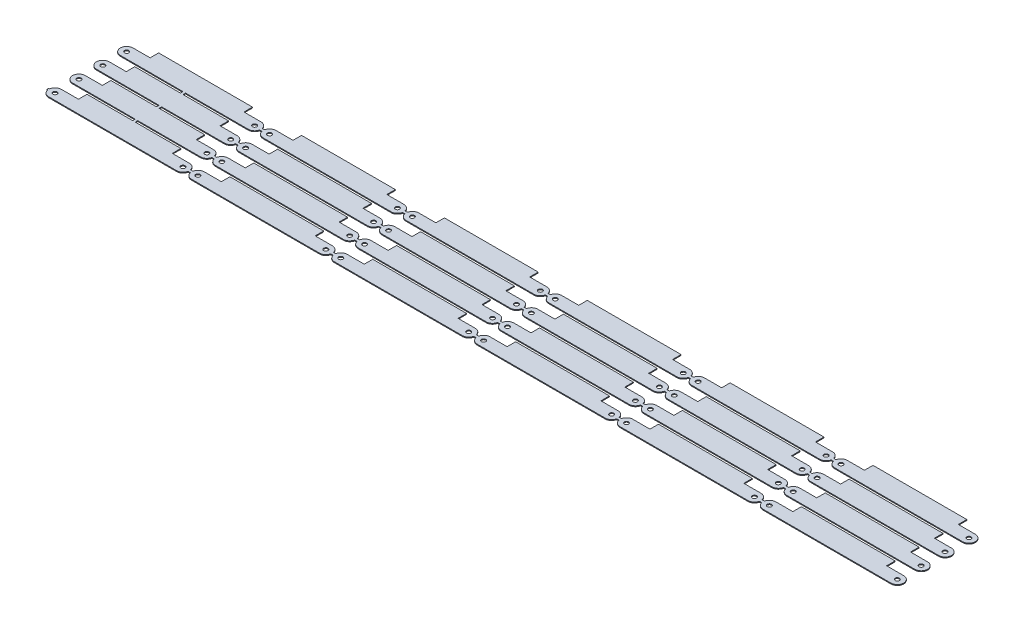
SolidWorks part; units mm, degrees
ref_plane "Front Plane" through (0, 0, 0) normal (0, 0, 1) x (1, 0, 0)
ref_plane "Top Plane" through (0, 0, 0) normal (0, 1, 0) x (1, 0, 0)
ref_plane "Right Plane" through (0, 0, 0) normal (1, 0, 0) x (0, 0, -1)
sketch "Sketch1" plane through (0, 0, 0) normal (0, 1, 0) x (1, 0, 0)
  line L0 (0, 0) -> (150, 0) construction
  line L1 (0, 7.5) -> (20, 7.5)
  line L2 (0, 7.5) -> (150, 7.5) construction
  line L3 (0, 7.5) -> (0, -7.5) construction
  line L4 (0, -7.5) -> (150, -7.5)
  line L5 (150, 7.5) -> (150, -7.5) construction
  line L6 (0, 7.5) -> (150, -7.5) construction
  line L7 (0, -7.5) -> (150, 7.5) construction
  line L8 (20, 7.5) -> (20, 17.5)
  line L9 (20, 17.5) -> (130, 17.5)
  line L10 (130, 17.5) -> (130, 7.5)
  line L11 (130, 7.5) -> (150, 7.5)
  line L12 (75, 0) -> (75, 17.5) construction
  line L13 (75, 17.5) -> (75, 20.5) construction
  line L14 (73.5, 17.5) -> (73.5, 20.5)
  line L15 (73.5, 20.5) -> (76.5, 20.5)
  line L16 (76.5, 20.5) -> (76.5, 17.5)
  line L17 (150, 0) -> (157.5, 0) construction
  line L18 (157.5, 0) -> (160.5, 0) construction
  line L19 (160.5, 1.5) -> (160.5, -1.5)
  line L20 (160.5, 1.5) -> (157.3485, 1.5)
  line L21 (160.5, -1.5) -> (157.3485, -1.5)
  line L22 (167.5, -7.5) -> (317.5, -7.5)
  line L23 (187.5, 17.5) -> (297.5, 17.5)
  line L24 (187.5, 7.5) -> (187.5, 17.5)
  line L25 (167.5, 7.5) -> (187.5, 7.5)
  line L26 (297.5, 7.5) -> (317.5, 7.5)
  line L27 (328, -1.5) -> (324.8485, -1.5)
  line L28 (328, 1.5) -> (324.8485, 1.5)
  line L29 (328, 1.5) -> (328, -1.5)
  line L30 (297.5, 17.5) -> (297.5, 7.5)
  line L31 (-7.5, 0) -> (-8.433, 0) construction
  line L32 (-8.433, 1) -> (-8.433, -1)
  line L33 (-8.433, -1) -> (-7.433, -1)
  line L34 (335, -7.5) -> (485, -7.5)
  line L35 (355, 17.5) -> (465, 17.5)
  line L36 (355, 7.5) -> (355, 17.5)
  line L37 (335, 7.5) -> (355, 7.5)
  line L38 (465, 7.5) -> (485, 7.5)
  line L39 (495.5, -1.5) -> (492.3485, -1.5)
  line L40 (495.5, 1.5) -> (492.3485, 1.5)
  line L41 (495.5, 1.5) -> (495.5, -1.5)
  line L42 (465, 17.5) -> (465, 7.5)
  line L44 (-8.433, 1) -> (-7.433, 1)
  line L46 (502.5, -7.5) -> (652.5, -7.5)
  line L47 (522.5, 17.5) -> (632.5, 17.5)
  line L48 (522.5, 7.5) -> (522.5, 17.5)
  line L49 (502.5, 7.5) -> (522.5, 7.5)
  line L50 (632.5, 7.5) -> (652.5, 7.5)
  line L51 (663, -1.5) -> (659.8485, -1.5)
  line L52 (663, 1.5) -> (659.8485, 1.5)
  line L53 (663, 1.5) -> (663, -1.5)
  line L54 (632.5, 17.5) -> (632.5, 7.5)
  line L58 (670, -7.5) -> (820, -7.5)
  line L59 (690, 17.5) -> (800, 17.5)
  line L60 (690, 7.5) -> (690, 17.5)
  line L61 (670, 7.5) -> (690, 7.5)
  line L62 (800, 7.5) -> (820, 7.5)
  line L63 (830.5, -1.5) -> (827.3485, -1.5)
  line L64 (830.5, 1.5) -> (827.3485, 1.5)
  line L65 (830.5, 1.5) -> (830.5, -1.5)
  line L66 (800, 17.5) -> (800, 7.5)
  line L70 (837.5, -7.5) -> (987.5, -7.5)
  line L71 (857.5, 17.5) -> (967.5, 17.5)
  line L72 (857.5, 7.5) -> (857.5, 17.5)
  line L73 (837.5, 7.5) -> (857.5, 7.5)
  line L74 (967.5, 7.5) -> (987.5, 7.5)
  line L78 (967.5, 17.5) -> (967.5, 7.5)
  line L82 (167.5, 20.5) -> (317.5, 20.5)
  line L83 (187.5, 45.5) -> (297.5, 45.5)
  line L84 (187.5, 35.5) -> (187.5, 45.5)
  line L85 (167.5, 35.5) -> (187.5, 35.5)
  line L86 (297.5, 35.5) -> (317.5, 35.5)
  line L87 (328, 26.5) -> (324.8485, 26.5)
  line L88 (328, 29.5) -> (324.8485, 29.5)
  line L89 (328, 29.5) -> (328, 26.5)
  line L90 (297.5, 45.5) -> (297.5, 35.5)
  line L94 (335, 20.5) -> (485, 20.5)
  line L95 (355, 45.5) -> (465, 45.5)
  line L96 (355, 35.5) -> (355, 45.5)
  line L97 (335, 35.5) -> (355, 35.5)
  line L98 (465, 35.5) -> (485, 35.5)
  line L99 (495.5, 26.5) -> (492.3485, 26.5)
  line L100 (495.5, 29.5) -> (492.3485, 29.5)
  line L101 (495.5, 29.5) -> (495.5, 26.5)
  line L102 (465, 45.5) -> (465, 35.5)
  line L106 (502.5, 20.5) -> (652.5, 20.5)
  line L107 (522.5, 45.5) -> (632.5, 45.5)
  line L108 (522.5, 35.5) -> (522.5, 45.5)
  line L109 (502.5, 35.5) -> (522.5, 35.5)
  line L110 (632.5, 35.5) -> (652.5, 35.5)
  line L111 (663, 26.5) -> (659.8485, 26.5)
  line L112 (663, 29.5) -> (659.8485, 29.5)
  line L113 (663, 29.5) -> (663, 26.5)
  line L114 (632.5, 45.5) -> (632.5, 35.5)
  line L118 (670, 20.5) -> (820, 20.5)
  line L119 (690, 45.5) -> (800, 45.5)
  line L120 (690, 35.5) -> (690, 45.5)
  line L121 (670, 35.5) -> (690, 35.5)
  line L122 (800, 35.5) -> (820, 35.5)
  line L123 (830.5, 26.5) -> (827.3485, 26.5)
  line L124 (830.5, 29.5) -> (827.3485, 29.5)
  line L125 (830.5, 29.5) -> (830.5, 26.5)
  line L126 (800, 45.5) -> (800, 35.5)
  line L130 (837.5, 20.5) -> (987.5, 20.5)
  line L131 (857.5, 45.5) -> (967.5, 45.5)
  line L132 (857.5, 35.5) -> (857.5, 45.5)
  line L133 (837.5, 35.5) -> (857.5, 35.5)
  line L134 (967.5, 35.5) -> (987.5, 35.5)
  line L138 (967.5, 45.5) -> (967.5, 35.5)
  line L142 (167.5, 48.5) -> (317.5, 48.5)
  line L143 (187.5, 73.5) -> (297.5, 73.5)
  line L144 (187.5, 63.5) -> (187.5, 73.5)
  line L145 (167.5, 63.5) -> (187.5, 63.5)
  line L146 (297.5, 63.5) -> (317.5, 63.5)
  line L147 (328, 54.5) -> (324.8485, 54.5)
  line L148 (328, 57.5) -> (324.8485, 57.5)
  line L149 (328, 57.5) -> (328, 54.5)
  line L150 (297.5, 73.5) -> (297.5, 63.5)
  line L154 (335, 48.5) -> (485, 48.5)
  line L155 (355, 73.5) -> (465, 73.5)
  line L156 (355, 63.5) -> (355, 73.5)
  line L157 (335, 63.5) -> (355, 63.5)
  line L158 (465, 63.5) -> (485, 63.5)
  line L159 (495.5, 54.5) -> (492.3485, 54.5)
  line L160 (495.5, 57.5) -> (492.3485, 57.5)
  line L161 (495.5, 57.5) -> (495.5, 54.5)
  line L162 (465, 73.5) -> (465, 63.5)
  line L166 (502.5, 48.5) -> (652.5, 48.5)
  line L167 (522.5, 73.5) -> (632.5, 73.5)
  line L168 (522.5, 63.5) -> (522.5, 73.5)
  line L169 (502.5, 63.5) -> (522.5, 63.5)
  line L170 (632.5, 63.5) -> (652.5, 63.5)
  line L171 (663, 54.5) -> (659.8485, 54.5)
  line L172 (663, 57.5) -> (659.8485, 57.5)
  line L173 (663, 57.5) -> (663, 54.5)
  line L174 (632.5, 73.5) -> (632.5, 63.5)
  line L178 (670, 48.5) -> (820, 48.5)
  line L179 (690, 73.5) -> (800, 73.5)
  line L180 (690, 63.5) -> (690, 73.5)
  line L181 (670, 63.5) -> (690, 63.5)
  line L182 (800, 63.5) -> (820, 63.5)
  line L183 (830.5, 54.5) -> (827.3485, 54.5)
  line L184 (830.5, 57.5) -> (827.3485, 57.5)
  line L185 (830.5, 57.5) -> (830.5, 54.5)
  line L186 (800, 73.5) -> (800, 63.5)
  line L190 (837.5, 48.5) -> (987.5, 48.5)
  line L191 (857.5, 73.5) -> (967.5, 73.5)
  line L192 (857.5, 63.5) -> (857.5, 73.5)
  line L193 (837.5, 63.5) -> (857.5, 63.5)
  line L194 (967.5, 63.5) -> (987.5, 63.5)
  line L198 (967.5, 73.5) -> (967.5, 63.5)
  line L202 (167.5, 76.5) -> (317.5, 76.5)
  line L203 (187.5, 101.5) -> (297.5, 101.5)
  line L204 (187.5, 91.5) -> (187.5, 101.5)
  line L205 (167.5, 91.5) -> (187.5, 91.5)
  line L206 (297.5, 91.5) -> (317.5, 91.5)
  line L207 (328, 82.5) -> (324.8485, 82.5)
  line L208 (328, 85.5) -> (324.8485, 85.5)
  line L209 (328, 85.5) -> (328, 82.5)
  line L210 (297.5, 101.5) -> (297.5, 91.5)
  line L214 (335, 76.5) -> (485, 76.5)
  line L215 (355, 101.5) -> (465, 101.5)
  line L216 (355, 91.5) -> (355, 101.5)
  line L217 (335, 91.5) -> (355, 91.5)
  line L218 (465, 91.5) -> (485, 91.5)
  line L219 (495.5, 82.5) -> (492.3485, 82.5)
  line L220 (495.5, 85.5) -> (492.3485, 85.5)
  line L221 (495.5, 85.5) -> (495.5, 82.5)
  line L222 (465, 101.5) -> (465, 91.5)
  line L226 (502.5, 76.5) -> (652.5, 76.5)
  line L227 (522.5, 101.5) -> (632.5, 101.5)
  line L228 (522.5, 91.5) -> (522.5, 101.5)
  line L229 (502.5, 91.5) -> (522.5, 91.5)
  line L230 (632.5, 91.5) -> (652.5, 91.5)
  line L231 (663, 82.5) -> (659.8485, 82.5)
  line L232 (663, 85.5) -> (659.8485, 85.5)
  line L233 (663, 85.5) -> (663, 82.5)
  line L234 (632.5, 101.5) -> (632.5, 91.5)
  line L238 (670, 76.5) -> (820, 76.5)
  line L239 (690, 101.5) -> (800, 101.5)
  line L240 (690, 91.5) -> (690, 101.5)
  line L241 (670, 91.5) -> (690, 91.5)
  line L242 (800, 91.5) -> (820, 91.5)
  line L243 (830.5, 82.5) -> (827.3485, 82.5)
  line L244 (830.5, 85.5) -> (827.3485, 85.5)
  line L245 (830.5, 85.5) -> (830.5, 82.5)
  line L246 (800, 101.5) -> (800, 91.5)
  line L250 (837.5, 76.5) -> (987.5, 76.5)
  line L251 (857.5, 101.5) -> (967.5, 101.5)
  line L252 (857.5, 91.5) -> (857.5, 101.5)
  line L253 (837.5, 91.5) -> (857.5, 91.5)
  line L254 (967.5, 91.5) -> (987.5, 91.5)
  line L258 (967.5, 101.5) -> (967.5, 91.5)
  line L262 (0, 20.5) -> (150, 20.5)
  line L263 (20, 45.5) -> (130, 45.5)
  line L264 (20, 35.5) -> (20, 45.5)
  line L265 (0, 35.5) -> (20, 35.5)
  line L266 (130, 35.5) -> (150, 35.5)
  line L267 (160.5, 26.5) -> (157.3485, 26.5)
  line L268 (160.5, 29.5) -> (157.3485, 29.5)
  line L269 (160.5, 29.5) -> (160.5, 26.5)
  line L270 (130, 45.5) -> (130, 35.5)
  line L271 (73.5, 45.5) -> (73.5, 48.5)
  line L272 (73.5, 48.5) -> (76.5, 48.5)
  line L273 (76.5, 48.5) -> (76.5, 45.5)
  line L274 (0, 48.5) -> (150, 48.5)
  line L275 (20, 73.5) -> (130, 73.5)
  line L276 (20, 63.5) -> (20, 73.5)
  line L277 (0, 63.5) -> (20, 63.5)
  line L278 (130, 63.5) -> (150, 63.5)
  line L279 (160.5, 54.5) -> (157.3485, 54.5)
  line L280 (160.5, 57.5) -> (157.3485, 57.5)
  line L281 (160.5, 57.5) -> (160.5, 54.5)
  line L282 (130, 73.5) -> (130, 63.5)
  line L283 (73.5, 73.5) -> (73.5, 76.5)
  line L284 (73.5, 76.5) -> (76.5, 76.5)
  line L285 (76.5, 76.5) -> (76.5, 73.5)
  line L286 (0, 76.5) -> (150, 76.5)
  line L287 (20, 101.5) -> (130, 101.5)
  line L288 (20, 91.5) -> (20, 101.5)
  line L289 (0, 91.5) -> (20, 91.5)
  line L290 (130, 91.5) -> (150, 91.5)
  line L291 (160.5, 82.5) -> (157.3485, 82.5)
  line L292 (160.5, 85.5) -> (157.3485, 85.5)
  line L293 (160.5, 85.5) -> (160.5, 82.5)
  line L294 (130, 101.5) -> (130, 91.5)
  line L298 (76.5, 104.5) -> (76.5, 101.5) [skipped]
  line L299 (73.5, 101.5) -> (73.5, 104.5) [skipped]
  line L300 (73.5, 104.5) -> (76.5, 104.5) [skipped]
  line L301 (241, 104.5) -> (244, 104.5) [skipped]
  line L302 (408.5, 104.5) -> (411.5, 104.5) [skipped]
  line L303 (576, 104.5) -> (579, 104.5) [skipped]
  line L304 (241, 101.5) -> (241, 104.5) [skipped]
  line L305 (244, 104.5) -> (244, 101.5) [skipped]
  line L306 (408.5, 101.5) -> (408.5, 104.5) [skipped]
  line L307 (411.5, 104.5) -> (411.5, 101.5) [skipped]
  line L308 (579, 104.5) -> (579, 101.5) [skipped]
  line L309 (576, 101.5) -> (576, 104.5) [skipped]
  line L310 (746.5, 104.5) -> (746.5, 101.5) [skipped]
  line L311 (743.5, 101.5) -> (743.5, 104.5) [skipped]
  line L312 (743.5, 104.5) -> (746.5, 104.5) [skipped]
  line L313 (911, 101.5) -> (911, 104.5) [skipped]
  line L314 (911, 104.5) -> (914, 104.5) [skipped]
  line L315 (914, 104.5) -> (914, 101.5) [skipped]
  line L316 (998, -1.5) -> (994.8485, -1.5) [skipped]
  line L317 (998, 1.5) -> (994.8485, 1.5) [skipped]
  line L318 (998, 1.5) -> (998, -1.5) [skipped]
  line L319 (998, 26.5) -> (994.8485, 26.5) [skipped]
  line L320 (998, 29.5) -> (994.8485, 29.5) [skipped]
  line L321 (998, 29.5) -> (998, 26.5) [skipped]
  line L322 (998, 54.5) -> (994.8485, 54.5) [skipped]
  line L323 (998, 57.5) -> (994.8485, 57.5) [skipped]
  line L324 (998, 57.5) -> (998, 54.5) [skipped]
  line L325 (998, 82.5) -> (994.8485, 82.5) [skipped]
  line L326 (998, 85.5) -> (994.8485, 85.5) [skipped]
  line L327 (998, 85.5) -> (998, 82.5) [skipped]
  line L328 (241, 73.5) -> (241, 76.5) [skipped]
  line L329 (244, 76.5) -> (244, 73.5) [skipped]
  line L330 (241, 76.5) -> (244, 76.5) [skipped]
  line L331 (241, 20.5) -> (244, 20.5) [skipped]
  line L332 (241, 17.5) -> (241, 20.5) [skipped]
  line L333 (244, 20.5) -> (244, 17.5) [skipped]
  line L334 (241, 45.5) -> (241, 48.5) [skipped]
  line L335 (241, 48.5) -> (244, 48.5) [skipped]
  line L336 (244, 48.5) -> (244, 45.5) [skipped]
  line L337 (408.5, 20.5) -> (411.5, 20.5) [skipped]
  line L338 (411.5, 20.5) -> (411.5, 17.5) [skipped]
  line L339 (408.5, 17.5) -> (408.5, 20.5) [skipped]
  line L340 (411.5, 48.5) -> (411.5, 45.5) [skipped]
  line L341 (408.5, 45.5) -> (408.5, 48.5) [skipped]
  line L342 (408.5, 48.5) -> (411.5, 48.5) [skipped]
  line L343 (408.5, 73.5) -> (408.5, 76.5) [skipped]
  line L344 (411.5, 76.5) -> (411.5, 73.5) [skipped]
  line L345 (408.5, 76.5) -> (411.5, 76.5) [skipped]
  line L346 (746.5, 20.5) -> (746.5, 17.5) [skipped]
  line L347 (743.5, 17.5) -> (743.5, 20.5) [skipped]
  line L348 (743.5, 20.5) -> (746.5, 20.5) [skipped]
  line L349 (746.5, 48.5) -> (746.5, 45.5) [skipped]
  line L350 (743.5, 48.5) -> (746.5, 48.5) [skipped]
  line L351 (743.5, 45.5) -> (743.5, 48.5) [skipped]
  line L352 (746.5, 76.5) -> (746.5, 73.5) [skipped]
  line L353 (743.5, 76.5) -> (746.5, 76.5) [skipped]
  line L354 (743.5, 73.5) -> (743.5, 76.5) [skipped]
  line L355 (914, 20.5) -> (914, 17.5) [skipped]
  line L356 (911, 20.5) -> (914, 20.5) [skipped]
  line L357 (911, 17.5) -> (911, 20.5) [skipped]
  line L358 (914, 48.5) -> (914, 45.5) [skipped]
  line L359 (911, 45.5) -> (911, 48.5) [skipped]
  line L360 (911, 48.5) -> (914, 48.5) [skipped]
  line L361 (914, 76.5) -> (914, 73.5) [skipped]
  line L362 (911, 76.5) -> (914, 76.5) [skipped]
  line L363 (911, 73.5) -> (911, 76.5) [skipped]
  line L364 (579, 20.5) -> (579, 17.5) [skipped]
  line L365 (576, 17.5) -> (576, 20.5) [skipped]
  line L366 (576, 20.5) -> (579, 20.5) [skipped]
  line L367 (579, 48.5) -> (579, 45.5) [skipped]
  line L368 (576, 48.5) -> (579, 48.5) [skipped]
  line L369 (576, 45.5) -> (576, 48.5) [skipped]
  line L370 (579, 76.5) -> (579, 73.5) [skipped]
  line L371 (576, 76.5) -> (579, 76.5) [skipped]
  line L372 (576, 73.5) -> (576, 76.5) [skipped]
  circle A0 centre (0, 0) radius 2.5
  circle A1 centre (150, 0) radius 2.5
  arc A2 (0, 7.5) -> (0, -7.5) centre (0, 0) ccw
  arc A3 (150, -7.5) -> (150, 7.5) centre (150, 0) ccw
  circle A4 centre (167.5, 0) radius 2.5
  arc A5 (167.5, 7.5) -> (167.5, -7.5) centre (167.5, 0) ccw
  arc A6 (317.5, -7.5) -> (317.5, 7.5) centre (317.5, 0) ccw
  circle A7 centre (317.5, 0) radius 2.5
  circle A8 centre (335, 0) radius 2.5
  arc A9 (335, 7.5) -> (335, -7.5) centre (335, 0) ccw
  arc A10 (485, -7.5) -> (485, 7.5) centre (485, 0) ccw
  circle A11 centre (485, 0) radius 2.5
  circle A12 centre (502.5, 0) radius 2.5
  arc A13 (502.5, 7.5) -> (502.5, -7.5) centre (502.5, 0) ccw
  arc A14 (652.5, -7.5) -> (652.5, 7.5) centre (652.5, 0) ccw
  circle A15 centre (652.5, 0) radius 2.5
  circle A16 centre (670, 0) radius 2.5
  arc A17 (670, 7.5) -> (670, -7.5) centre (670, 0) ccw
  arc A18 (820, -7.5) -> (820, 7.5) centre (820, 0) ccw
  circle A19 centre (820, 0) radius 2.5
  circle A20 centre (837.5, 0) radius 2.5
  arc A21 (837.5, 7.5) -> (837.5, -7.5) centre (837.5, 0) ccw
  arc A22 (987.5, -7.5) -> (987.5, 7.5) centre (987.5, 0) ccw
  circle A23 centre (987.5, 0) radius 2.5
  circle A24 centre (167.5, 28) radius 2.5
  arc A25 (167.5, 35.5) -> (167.5, 20.5) centre (167.5, 28) ccw
  arc A26 (317.5, 20.5) -> (317.5, 35.5) centre (317.5, 28) ccw
  circle A27 centre (317.5, 28) radius 2.5
  circle A28 centre (335, 28) radius 2.5
  arc A29 (335, 35.5) -> (335, 20.5) centre (335, 28) ccw
  arc A30 (485, 20.5) -> (485, 35.5) centre (485, 28) ccw
  circle A31 centre (485, 28) radius 2.5
  circle A32 centre (502.5, 28) radius 2.5
  arc A33 (502.5, 35.5) -> (502.5, 20.5) centre (502.5, 28) ccw
  arc A34 (652.5, 20.5) -> (652.5, 35.5) centre (652.5, 28) ccw
  circle A35 centre (652.5, 28) radius 2.5
  circle A36 centre (670, 28) radius 2.5
  arc A37 (670, 35.5) -> (670, 20.5) centre (670, 28) ccw
  arc A38 (820, 20.5) -> (820, 35.5) centre (820, 28) ccw
  circle A39 centre (820, 28) radius 2.5
  circle A40 centre (837.5, 28) radius 2.5
  arc A41 (837.5, 35.5) -> (837.5, 20.5) centre (837.5, 28) ccw
  arc A42 (987.5, 20.5) -> (987.5, 35.5) centre (987.5, 28) ccw
  circle A43 centre (987.5, 28) radius 2.5
  circle A44 centre (167.5, 56) radius 2.5
  arc A45 (167.5, 63.5) -> (167.5, 48.5) centre (167.5, 56) ccw
  arc A46 (317.5, 48.5) -> (317.5, 63.5) centre (317.5, 56) ccw
  circle A47 centre (317.5, 56) radius 2.5
  circle A48 centre (335, 56) radius 2.5
  arc A49 (335, 63.5) -> (335, 48.5) centre (335, 56) ccw
  arc A50 (485, 48.5) -> (485, 63.5) centre (485, 56) ccw
  circle A51 centre (485, 56) radius 2.5
  circle A52 centre (502.5, 56) radius 2.5
  arc A53 (502.5, 63.5) -> (502.5, 48.5) centre (502.5, 56) ccw
  arc A54 (652.5, 48.5) -> (652.5, 63.5) centre (652.5, 56) ccw
  circle A55 centre (652.5, 56) radius 2.5
  circle A56 centre (670, 56) radius 2.5
  arc A57 (670, 63.5) -> (670, 48.5) centre (670, 56) ccw
  arc A58 (820, 48.5) -> (820, 63.5) centre (820, 56) ccw
  circle A59 centre (820, 56) radius 2.5
  circle A60 centre (837.5, 56) radius 2.5
  arc A61 (837.5, 63.5) -> (837.5, 48.5) centre (837.5, 56) ccw
  arc A62 (987.5, 48.5) -> (987.5, 63.5) centre (987.5, 56) ccw
  circle A63 centre (987.5, 56) radius 2.5
  circle A64 centre (167.5, 84) radius 2.5
  arc A65 (167.5, 91.5) -> (167.5, 76.5) centre (167.5, 84) ccw
  arc A66 (317.5, 76.5) -> (317.5, 91.5) centre (317.5, 84) ccw
  circle A67 centre (317.5, 84) radius 2.5
  circle A68 centre (335, 84) radius 2.5
  arc A69 (335, 91.5) -> (335, 76.5) centre (335, 84) ccw
  arc A70 (485, 76.5) -> (485, 91.5) centre (485, 84) ccw
  circle A71 centre (485, 84) radius 2.5
  circle A72 centre (502.5, 84) radius 2.5
  arc A73 (502.5, 91.5) -> (502.5, 76.5) centre (502.5, 84) ccw
  arc A74 (652.5, 76.5) -> (652.5, 91.5) centre (652.5, 84) ccw
  circle A75 centre (652.5, 84) radius 2.5
  circle A76 centre (670, 84) radius 2.5
  arc A77 (670, 91.5) -> (670, 76.5) centre (670, 84) ccw
  arc A78 (820, 76.5) -> (820, 91.5) centre (820, 84) ccw
  circle A79 centre (820, 84) radius 2.5
  circle A80 centre (837.5, 84) radius 2.5
  arc A81 (837.5, 91.5) -> (837.5, 76.5) centre (837.5, 84) ccw
  arc A82 (987.5, 76.5) -> (987.5, 91.5) centre (987.5, 84) ccw
  circle A83 centre (987.5, 84) radius 2.5
  circle A84 centre (0, 28) radius 2.5
  arc A85 (0, 35.5) -> (0, 20.5) centre (0, 28) ccw
  arc A86 (150, 20.5) -> (150, 35.5) centre (150, 28) ccw
  circle A87 centre (150, 28) radius 2.5
  circle A88 centre (0, 56) radius 2.5
  arc A89 (0, 63.5) -> (0, 48.5) centre (0, 56) ccw
  arc A90 (150, 48.5) -> (150, 63.5) centre (150, 56) ccw
  circle A91 centre (150, 56) radius 2.5
  circle A92 centre (0, 84) radius 2.5
  arc A93 (0, 91.5) -> (0, 76.5) centre (0, 84) ccw
  arc A94 (150, 76.5) -> (150, 91.5) centre (150, 84) ccw
  circle A95 centre (150, 84) radius 2.5
  point P5 (75, 0)
  dimension "D3" = 5
  dimension "D1" = 150
  dimension "D2" = 15
  dimension "D4" = 10
  dimension "D5" = 20
  dimension "D6" = 3
  dimension "D7" = 3
  dimension "D8" = 3
  dimension "D9" = 3
  dimension "D12" = 1
  dimension "D13" = 2
  dimension "D10" = 6
  dimension "D11" = 4
extrude "Boss-Extrude1" add sketch "Sketch1" along normal blind 1 contours L4 A3 L11 L10 L9 L8 L1 A2 A0 A1 | L16 L15 L14 L9 | L262 A86 L266 L270 L263 L264 L265 A85 L15 A87 A84 | L273 L272 L271 L263 | L274 A90 L278 L282 L275 L276 L277 A89 L272 A91 A88 | L285 L284 L283 L275 | L286 A94 L290 L294 L287 L288 L289 A93 L284 A95 A92 | A94 L291 A65 L292 | L202 A66 L206 L210 L203 L204 L205 A65 L292 L293 L291 A67 A64 | A90 L279 A45 L280 | L142 A46 L146 L150 L143 L144 L145 A45 L280 L281 L279 A47 A44 | A86 L267 A25 L268 | L82 A26 L86 L90 L83 L84 L85 A25 L268 L269 L267 A27 A24 | L22 A6 L26 L30 L23 L24 L25 A5 L20 L19 L21 A7 A4 | L268 A25 L267 L269 | L292 A65 L291 L293 | L280 A45 L279 L281 | A9 L28 A6 L27 | L28 A9 L27 L29 | L34 A10 L38 L42 L35 L36 L37 A9 L28 L29 L27 A11 A8 | A29 L88 A26 L87 | L88 A29 L87 L89 | L94 A30 L98 L102 L95 L96 L97 A29 L88 L89 L87 A31 A28 | A49 L148 A46 L147 | L148 A49 L147 L149 | L154 A50 L158 L162 L155 L156 L157 A49 L148 L149 L147 A51 A48 | A69 L208 A66 L207 | L208 A69 L207 L209 | L214 A70 L218 L222 L215 L216 L217 A69 L208 L209 L207 A71 A68 | A13 L40 A10 L39 | L46 A14 L50 L54 L47 L48 L49 A13 L40 L41 L39 A15 A12 | L40 A13 L39 L41 | A33 L100 A30 L99 | L100 A33 L99 L101 | L106 A34 L110 L114 L107 L108 L109 A33 L100 L101 L99 A35 A32 | A53 L160 A50 L159 | L160 A53 L159 L161 | L166 A54 L170 L174 L167 L168 L169 A53 L160 L161 L159 A55 A52 | A73 L220 A70 L219 | L220 A73 L219 L221 | L226 A74 L230 L234 L227 L228 L229 A73 L220 L221 L219 A75 A72 | A17 L52 A14 L51 | L52 A17 L51 L53 | L58 A18 L62 L66 L59 L60 L61 A17 L52 L53 L51 A19 A16 | A37 L112 A34 L111 | L112 A37 L111 L113 | L118 A38 L122 L126 L119 L120 L121 A37 L112 L113 L111 A39 A36 | A57 L172 A54 L171 | L172 A57 L171 L173 | L178 A58 L182 L186 L179 L180 L181 A57 L172 L173 L171 A59 A56 | A77 L232 A74 L231 | L232 A77 L231 L233 | L238 A78 L242 L246 L239 L240 L241 A77 L232 L233 L231 A79 A76 | A21 L64 A18 L63 | L64 A21 L63 L65 | L70 A22 L74 L78 L71 L72 L73 A21 L64 L65 L63 A23 A20 | A41 L124 A38 L123 | L124 A41 L123 L125 | L130 A42 L134 L138 L131 L132 L133 A41 L124 L125 L123 A43 A40 | A81 L244 A78 L243 | L244 A81 L243 L245 | L250 A82 L254 L258 L251 L252 L253 A81 L244 L245 L243 A83 A80 | A61 L184 A58 L183 | L184 A61 L183 L185 | L190 A62 L194 L198 L191 L192 L193 A61 L184 L185 L183 A63 A60 | A5 L20 A3 L21 | L20 A5 L21 L19 | A2 L44 L32 L33 region at (75, 0, -3.9427) region at (-7.9552, 0, 0) region at (75, 0, -19) region at (75, 0, -31.9427) region at (158.75, 0, 0) region at (160.2729, 0, 0) region at (242.5318, 0, -3.9442) region at (158.75, 0, -28) region at (160.2729, 0, -28) region at (242.5318, 0, -31.9442) region at (75, 0, -47) region at (326.25, 0, 0) region at (75, 0, -59.9427) region at (327.7729, 0, 0) region at (410.0318, 0, -3.9442) region at (326.25, 0, -28) region at (158.75, 0, -56) region at (493.75, 0, 0) region at (242.5318, 0, -59.9442) region at (327.7729, 0, -28) region at (410.0318, 0, -31.9442) region at (160.2729, 0, -56) region at (495.2729, 0, 0) region at (577.5318, 0, -3.9442) region at (75, 0, -75) region at (75, 0, -87.9427) region at (326.25, 0, -56) region at (661.25, 0, 0) region at (327.7729, 0, -56) region at (410.0318, 0, -59.9442) region at (662.7729, 0, 0) region at (745.0318, 0, -3.9442) region at (493.75, 0, -28) region at (158.75, 0, -84) region at (495.2729, 0, -28) region at (577.5318, 0, -31.9442) region at (242.5318, 0, -87.9442) region at (160.2729, 0, -84) region at (828.75, 0, 0) region at (830.2729, 0, 0) region at (912.5318, 0, -3.9442) region at (493.75, 0, -56) region at (326.25, 0, -84) region at (661.25, 0, -28) region at (410.0318, 0, -87.9442) region at (495.2729, 0, -56) region at (577.5318, 0, -59.9442) region at (327.7729, 0, -84) region at (662.7729, 0, -28) region at (745.0318, 0, -31.9442) region at (493.75, 0, -84) region at (828.75, 0, -28) region at (495.2729, 0, -84) region at (577.5318, 0, -87.9442) region at (830.2729, 0, -28) region at (912.5318, 0, -31.9442) region at (661.25, 0, -56) region at (662.7729, 0, -56) region at (745.0318, 0, -59.9442) region at (661.25, 0, -84)
